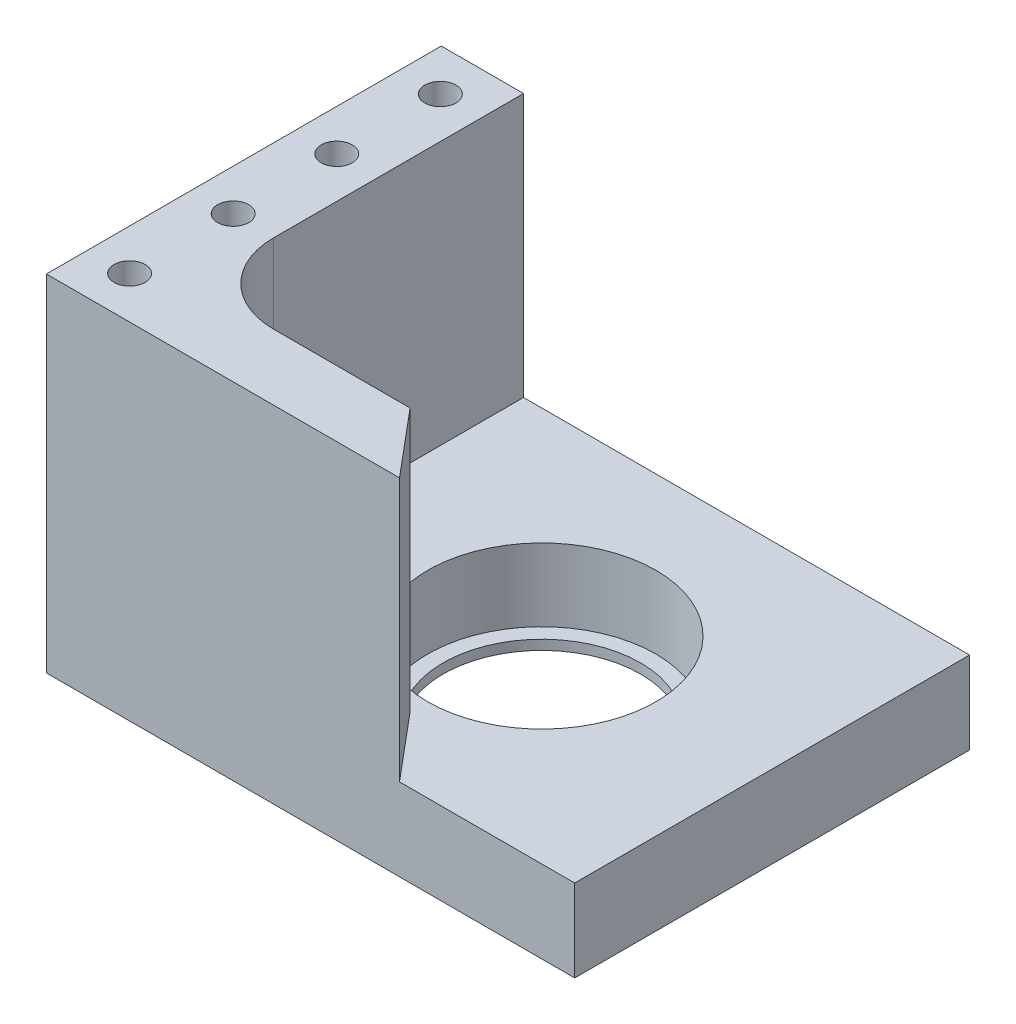
SolidWorks part; units mm, degrees
ref_plane "Front Plane" through (0, 0, 0) normal (0, 0, 1) x (1, 0, 0)
ref_plane "Top Plane" through (0, 0, 0) normal (0, 1, 0) x (1, 0, 0)
ref_plane "Right Plane" through (0, 0, 0) normal (1, 0, 0) x (0, 0, -1)
sketch "Sketch1" plane through (0, 0, 0) normal (0, 1, 0) x (1, 0, 0)
  line L0 (0, 0) -> (22.225, 0) construction
  line L1 (22.225, 19.05) -> (-28.75, 19.05)
  line L2 (22.225, 19.05) -> (22.225, -19.05)
  line L3 (22.225, -19.05) -> (-28.75, -19.05)
  line L4 (-28.75, 19.05) -> (-28.75, -19.05)
  line L5 (15.875, 12.7) -> (-9.525, -12.7) construction
  line L10 (15.875, 12.7) -> (-9.525, 12.7) construction
  line L11 (15.875, 12.7) -> (15.875, -12.7) construction
  line L12 (15.875, -12.7) -> (-9.525, -12.7) construction
  line L13 (-9.525, 12.7) -> (-9.525, -12.7) construction
  line L14 (-34.925, 12.7) -> (-9.525, 12.7) construction
  circle A0 centre (0, 0) radius 11 construction
  point P7 (3.175, 0)
  line B0 (12.875, 6.35) -> (18.875, 6.35)
  line B1 (12.875, 6.35) -> (12.875, 19.05)
  line B2 (12.875, 19.05) -> (18.875, 19.05)
  line B3 (18.875, 6.35) -> (18.875, 19.05)
  line B4 (12.875, 6.35) -> (18.875, 19.05) construction
  line B5 (12.875, 19.05) -> (18.875, 6.35) construction
  line B6 (-12.525, 6.35) -> (-6.525, 6.35)
  line B7 (-12.525, 6.35) -> (-12.525, 19.05)
  line B8 (-6.525, 6.35) -> (-6.525, 19.05)
  line B9 (-12.525, 6.35) -> (-6.525, 19.05) construction
  line B10 (-12.525, 19.05) -> (-6.525, 6.35) construction
  line B11 (-12.525, -19.05) -> (-12.525, -6.35)
  line B12 (-12.525, -6.35) -> (-6.525, -6.35)
  line B13 (-6.525, -19.05) -> (-6.525, -6.35)
  line B14 (-12.525, -19.05) -> (-6.525, -6.35) construction
  line B15 (-12.525, -6.35) -> (-6.525, -19.05) construction
  line B16 (12.875, -19.05) -> (12.875, -6.35)
  line B17 (12.875, -6.35) -> (18.875, -6.35)
  line B18 (18.875, -19.05) -> (18.875, -6.35)
  line B19 (12.875, -19.05) -> (18.875, -6.35) construction
  line B20 (12.875, -6.35) -> (18.875, -19.05) construction
  line B21 (-37.925, 6.35) -> (-31.925, 6.35)
  line B22 (-37.925, 6.35) -> (-37.925, 19.05)
  line B23 (-37.925, 19.05) -> (-31.925, 19.05)
  line B24 (-31.925, 6.35) -> (-31.925, 19.05)
  line B25 (-37.925, 6.35) -> (-31.925, 19.05) construction
  line B26 (-37.925, 19.05) -> (-31.925, 6.35) construction
  line B27 (-37.925, -19.05) -> (-31.925, -19.05)
  line B28 (-37.925, -19.05) -> (-37.925, -6.35)
  line B29 (-37.925, -6.35) -> (-31.925, -6.35)
  line B30 (-31.925, -19.05) -> (-31.925, -6.35)
  line B31 (-37.925, -19.05) -> (-31.925, -6.35) construction
  line B32 (-37.925, -6.35) -> (-31.925, -19.05) construction
  dimension "D2" = 22
  dimension "D1" = 38.1
  dimension "D3" = 25.4
  dimension "D4" = 25.4
  dimension "D5" = 3.175
  dimension "D6" = 22.225
  dimension "D7" = 3.175
sketch_block_instance "SlotGeo-1"
sketch_block "SlotGeo" parameters "D1"=3.1784, "D2"=8.2348
sketch_block_instance "SlotGeo-2"
sketch_block_instance "SlotGeo-3"
sketch_block_instance "SlotGeo-4"
sketch_block_instance "SlotGeo-5"
sketch_block_instance "SlotGeo-6"
extrude "Base" add sketch "Sketch1" along normal blind 7.9375 contours L2 L1 L4 L3
ref_plane "TopBasePlate" through (0, -3.175, 0) normal (0, -1, 0) x (-1, 0, 0)
sketch "Sketch2" plane through (0, 7.9375, 0) normal (0, 1, 0) x (1, 0, 0)
  circle A0 centre (0, 0) radius 11
  dimension "D1" = 22
extrude "Bearing Bore" cut sketch "Sketch2" against normal blind 7 contours A0
sketch "Sketch3" plane through (0, 0.9375, 0) normal (0, 1, 0) x (1, 0, 0)
  circle A0 centre (0, 0) radius 9.525
  dimension "D1" = 19.05
extrude "Thru Hole" cut sketch "Sketch3" against normal through all both and the other way through all
sketch "Sketch4" plane through (0, 7.9375, 0) normal (0, 1, 0) x (1, 0, 0)
  line L0 (22.225, 19.05) -> (-28.75, 19.05) construction
  line L1 (-28.75, -19.05) -> (-20.8125, -19.05)
  line L2 (-28.75, -19.05) -> (-28.75, 19.05)
  line L3 (-28.75, 19.05) -> (-20.8125, 19.05)
  line L4 (-20.8125, -19.05) -> (-20.8125, 19.05)
  dimension "D1" = 7.9375
extrude "Vertical" add sketch "Sketch4" along normal blind 25.4
sketch "Sketch5" plane through (-28.75, 0, 0) normal (-1, 0, 0) x (0, 0, 1)
  line L0 (-12.7, 19.225) -> (12.7, 19.225) construction
  line L1 (12.7, 19.225) -> (12.7, -3.175) construction
  line L3 (-20.955, -3.175) -> (20.955, -3.175) construction
  line L4 (21.5743, -6.175) -> (-23.6916, -6.175) construction
  line L5 (21.5743, -9.175) -> (-23.6916, -9.175) construction
  line L6 (21.5743, -9.175) -> (21.5743, -3.175) construction
  line L7 (21.5743, -3.175) -> (-23.6916, -3.175) construction
  line L8 (-23.6916, -9.175) -> (-23.6916, -3.175) construction
  line B0 (19.05, 16.225) -> (19.05, 22.225)
  line B1 (19.05, 16.225) -> (6.35, 16.225)
  line B2 (6.35, 16.225) -> (6.35, 22.225)
  line B3 (19.05, 22.225) -> (6.35, 22.225)
  line B4 (19.05, 16.225) -> (6.35, 22.225) construction
  line B5 (6.35, 16.225) -> (19.05, 22.225) construction
  line B6 (-6.35, 16.225) -> (-6.35, 22.225)
  line B7 (-6.35, 16.225) -> (-19.05, 16.225)
  line B8 (-6.35, 22.225) -> (-19.05, 22.225)
  line B9 (-6.35, 16.225) -> (-19.05, 22.225) construction
  line B10 (-19.05, 16.225) -> (-6.35, 22.225) construction
  dimension "D1" = 25.4
  dimension "D2" = 6
  dimension "D3" = 25.4
sketch_block_instance "SlotGeo-7"
sketch_block_instance "SlotGeo-8"
sketch "Sketch6" plane through (0, 33.3375, 0) normal (0, 1, 0) x (1, 0, 0)
  line L0 (-24.7812, 14.9904) -> (-24.7812, -14.9904) construction
  line L1 (-28.75, 0) -> (-20.8125, 0) construction
  line L9 (-28.75, 19.05) -> (-28.75, -19.05)
  line L10 (-28.75, -19.05) -> (-20.8125, -19.05)
  line L11 (-20.8125, -19.05) -> (-20.8125, 19.05)
  line L12 (-20.8125, 19.05) -> (-28.75, 19.05)
  line L13 (-28.75, 19.05) -> (-28.75, -19.05) construction
  line L14 (-28.75, -19.05) -> (-20.8125, -19.05) construction
  line L15 (-20.8125, -19.05) -> (-20.8125, 19.05) construction
  line L16 (-20.8125, 19.05) -> (-28.75, 19.05) construction
  circle A0 centre (-24.7812, 14.9904) radius 1.5
  circle A1 centre (-24.7812, 4.9968) radius 1.5
  circle A2 centre (-24.7812, -14.9904) radius 1.5
  circle A3 centre (-24.7812, -4.9968) radius 1.5
  point P6 (-24.7812, 0)
  point P7 (-24.7812, 0)
  point P8 (-24.9136, 14.9904)
  point P15 (-24.9136, 14.9904)
  point P17 (-26.5213, 4.3764)
  point P19 (0, 0)
  point P20 (-26.1204, -4.8526)
  point P21 (0, 0)
  point P22 (-24.7812, -14.9904)
  dimension "D1" = 3
  dimension "D4" = 3
  dimension "D5" = 3
  dimension "D3" = 29.9808
  dimension "D6" = 9.9936
  dimension "D7" = 19.9872
sketch "Sketch7" plane through (-20.8125, 0, 0) normal (1, 0, 0) x (0, 0, -1)
  line L0 (-19.05, 7.9375) -> (19.05, 7.9375) construction
  line L1 (-19.05, 33.3375) -> (-12.7, 33.3375)
  line L2 (-19.05, 33.3375) -> (-19.05, 7.9375)
  line L3 (-19.05, 7.9375) -> (-12.7, 7.9375)
  line L4 (-12.7, 33.3375) -> (-12.7, 7.9375)
  point P5 (0, 0)
  dimension "D1" = 6.35
extrude "Arm Stop" add sketch "Sketch7" along normal blind 20.8026
sketch "Sketch8" plane through (0, 33.3375, 0) normal (0, 1, 0) x (1, 0, 0)
  line L0 (-0.0099, -12.7) -> (5.3184, -19.05)
  line L1 (22.225, -19.05) -> (-0.0099, -19.05) construction
  line L2 (5.3184, -19.05) -> (-0.0099, -19.05)
  line L3 (-0.0099, -19.05) -> (-0.0099, -12.7)
  dimension "D1" = 40
extrude "Angled Face" add sketch "Sketch8" against normal up to next
fillet "Fillet1" radius 7.62 1 edges at (-20.8125, 20.6375, 12.7)
extrude "Dowel Holes" cut sketch "Sketch6" against normal blind 7.008
equation "\"D4@Sketch6\"=\"D1@Sketch6\""
equation "\"D5@Sketch6\"=\"D1@Sketch6\""
equation "\"D6@Sketch6\"=\"D3@Sketch6\"/3"
equation "\"D7@Sketch6\"=2*\"D3@Sketch6\"/3"
